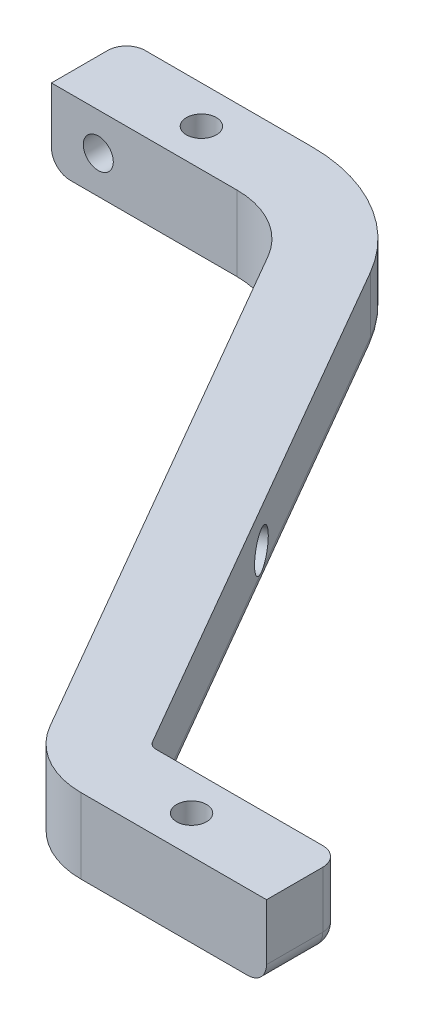
SolidWorks part; units mm, degrees
ref_plane "Plan de face" through (0, 0, 0) normal (0, 0, 1) x (1, 0, 0)
ref_plane "Plan de dessus" through (0, 0, 0) normal (0, 1, 0) x (1, 0, 0)
ref_plane "Plan de droite" through (0, 0, 0) normal (1, 0, 0) x (0, 0, -1)
sketch "Esquisse1" plane through (0, 0, 0) normal (0, 1, 0) x (1, 0, 0)
  line L0 (0, 0) -> (19.8038, 0)
  line L1 (27.5981, -4.5) -> (59.3523, -59.5)
  line L2 (67.1466, -64) -> (86.9504, -64)
  arc A0 (59.3523, -59.5) -> (67.1466, -64) centre (67.1466, -55) ccw
  arc A1 (19.8038, 0) -> (27.5981, -4.5) centre (19.8038, -9) cw
  point P9 (25, 0)
  dimension "D4" = 9
  dimension "D1" = 120
  dimension "D2" = 25
  dimension "D3" = 64
extrude "Extru.-Mince1" add sketch "Esquisse1" along normal blind 8 thin thin type one direction reverse wall 8
sketch "Esquisse2" plane through (0, 8, 0) normal (0, 1, 0) x (1, 0, 0)
  line L0 (86.9504, -60) -> (74.9504, -60) construction
  line L1 (86.9504, -56) -> (86.9504, -64) construction
  line L3 (12, 4) -> (0, 4) construction
  line L4 (0, 0) -> (0, 8) construction
  circle A0 centre (74.9504, -60) radius 1.6
  circle A1 centre (12, 4) radius 1.6
  dimension "D1" = 3.2
  dimension "D2" = 12
extrude "Enlèv. mat.-Extru.1" cut sketch "Esquisse2" against normal through all
sketch "Esquisse3" plane through (0, 0, 0) normal (0, -1, 0) x (1, 0, 0)
  circle A0 centre (74.9504, 60) radius 2
  circle A1 centre (12, -4) radius 2
  dimension "D1" = 4
extrude "Enlèv. mat.-Extru.2" cut sketch "Esquisse3" against normal blind 5.5
sketch "Esquisse4" plane through (0, 0, 0) normal (0, 0, -1) x (-1, 0, 0)
  line L0 (0, 4) -> (-5, 4) construction
  line L2 (0, 8) -> (0, 0) construction
  circle A0 centre (-5, 4) radius 1.6
  dimension "D2" = 3.2
  dimension "D1" = 5
extrude "Enlèv. mat.-Extru.3" cut sketch "Esquisse4" along normal through all
sketch "Esquisse5" plane through (0, 0, -8) normal (0, 0, 1) x (1, 0, 0)
  circle A0 centre (5, 4) radius 2
  dimension "D1" = 4
extrude "Enlèv. mat.-Extru.4" cut sketch "Esquisse5" along normal blind 5.5
sketch "Esquisse7" plane through (18.75, 0, -10.8253) normal (-0.866, 0, 0.5) x (0.5, 0, 0.866)
  line L0 (17.6962, 0) -> (81.2047, 8) construction
  circle A0 centre (49.4504, 4) radius 1.6
  dimension "D1" = 3.2
extrude "Enlèv. mat.-Extru.5" cut sketch "Esquisse7" against normal through all
sketch "Esquisse8" plane through (25.6782, 0, -14.8253) normal (0.866, 0, -0.5) x (-0.5, 0, -0.866)
  circle A0 centre (-49.4504, 4) radius 2
  dimension "D1" = 4
extrude "Enlèv. mat.-Extru.6" cut sketch "Esquisse8" against normal blind 5.5
fillet "Congé1" radius 2 9 edges at (86.9504, 0, 60) (0, 0, -4) (9.9019, 0, -8) (28.3038, 0, -5.7224) (77.0485, 0, 56) (66.6466, 0, 55.866) (0, 4, -8) (86.9504, 4, 56) (50.4034, 0, 28)
move or copy body "Corps-Déplacer/Copier1" [suppressed] bodies to move or copy 107
